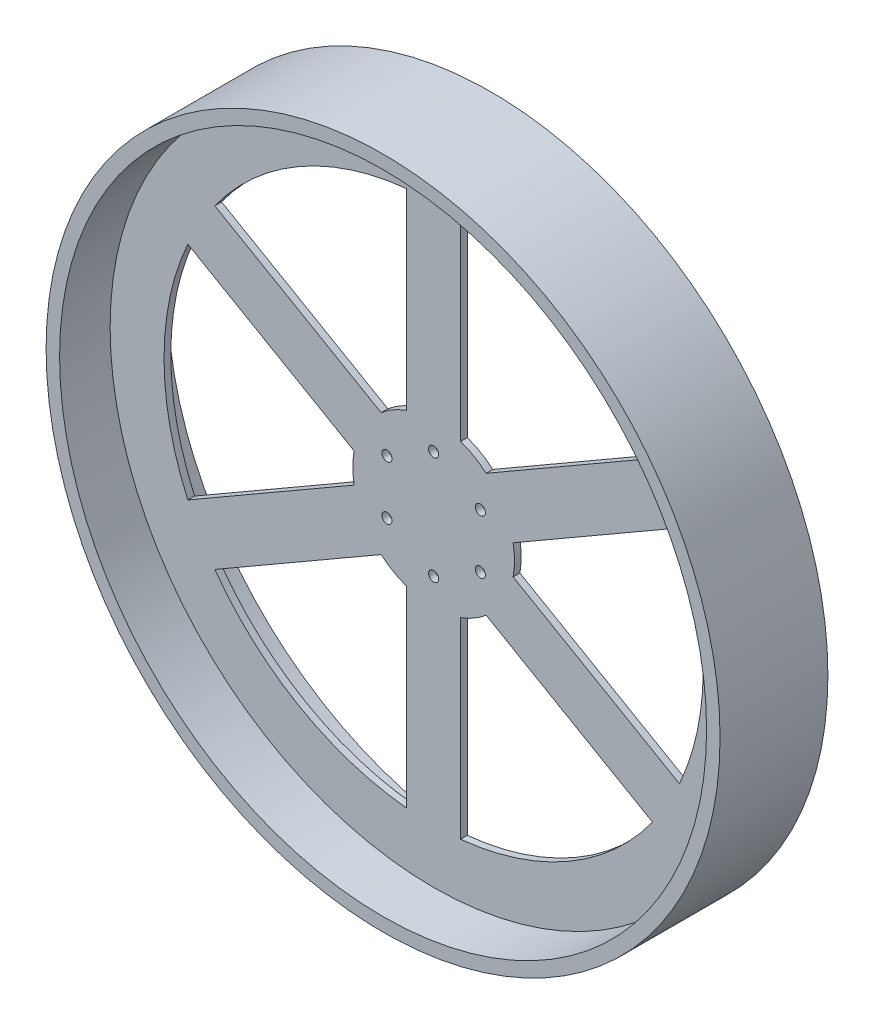
SolidWorks part; units mm, degrees
ref_plane "Front Plane" through (0, 0, 0) normal (0, 0, 1) x (1, 0, 0)
ref_plane "Top Plane" through (0, 0, 0) normal (0, 1, 0) x (1, 0, 0)
ref_plane "Right Plane" through (0, 0, 0) normal (1, 0, 0) x (0, 0, -1)
sketch "Sketch2" plane through (0, 0, 0) normal (0, 0, 1) x (1, 0, 0)
  line L0 (0, 0) -> (0, -254)
  line L1 (0, 0) -> (219.9705, -127)
  line L2 (97.2852, -85.497) -> (122.6852, -41.503) construction
  line L7 (-25.4, -127) -> (25.4, -127) construction
  line L8 (-25.4, -71.842) -> (-25.4, -252.7268)
  line L13 (25.4, -71.842) -> (25.4, -252.7268)
  line L14 (-74.917, -13.924) -> (-231.5678, -104.3664)
  line L15 (74.917, -13.924) -> (231.5678, -104.3664)
  line L16 (49.517, -57.9181) -> (206.1678, -148.3604)
  line L17 (-49.517, -57.9181) -> (-206.1678, -148.3604)
  line L18 (-49.517, 57.9181) -> (-206.1678, 148.3604)
  line L19 (-74.917, 13.924) -> (-231.5678, 104.3664)
  line L20 (25.4, 71.842) -> (25.4, 252.7268)
  line L21 (-25.4, 71.842) -> (-25.4, 252.7268)
  line L32 (74.917, 13.924) -> (231.5678, 104.3664)
  line L33 (49.517, 57.9181) -> (206.1678, 148.3604)
  circle A0 centre (0, 0) radius 304.8
  circle A1 centre (0, 0) radius 254
  circle A3 centre (0, 0) radius 254
  circle A5 centre (0, 0) radius 254
  circle A7 centre (0, 0) radius 254
  circle A9 centre (0, 0) radius 254
  circle A11 centre (0, 0) radius 254
  circle A12 centre (0, 0) radius 76.2
  point P5 (0, -127)
  point P10 (109.9852, -63.5)
  point P12 (109.9852, -63.5)
  point P14 (0, -127)
  point P17 (-25.4, -127)
  point P21 (25.4, -127)
  point P24 (97.2852, -85.497)
  point P28 (122.6852, -41.503)
  point P50 (0, 0)
  point P73 (0, 0)
  dimension "D1" = 60
  dimension "D3" = 609.6
  dimension "D2" = 508
  dimension "D4" = 152.4
  dimension "D5" = 50.8
  dimension "D6" = 3
extrude "Boss-Extrude1" add sketch "Sketch2" along direction (0, 0, 1) on the side of the normal blind 3.175 and the other way blind 3.175 contours A0 A1 | A1 | A1 | A1 | A1 L1 | L1 A1 | L0 A1 | A1 L0 | L0 L1 | L0 L1 | A1 region at (24.2552, -42.0113, 0) region at (-4.851, 8.4023, 0) region at (12.7362, -164.1659, 0) region at (-12.7362, -164.1659, 0) region at (148.54, -71.0531, 0) region at (135.8038, -93.1128, 0) region at (-142.1719, -82.083, 0) region at (142.1719, 82.083, 0) region at (-142.1719, 82.083, 0) region at (0, 164.1659, 0) region at (-296.179, 0, 0)
sketch "Sketch5" plane through (0, 0, 0) normal (0, 0, 1) x (1, 0, 0)
  circle A0 centre (0, 0) radius 317.5
  circle A1 centre (0, 0) radius 304.8
extrude "Boss-Extrude2" add sketch "Sketch5" along normal blind 50.8 and the other way blind 50.8
sketch "Sketch6" plane through (0, 0, 3.175) normal (0, 0, 1) x (1, 0, 0)
  circle A1 centre (0, 50.8) radius 4.7625
  circle A2 centre (43.9941, 25.4) radius 4.7625
  circle A3 centre (43.9941, -25.4) radius 4.7625
  circle A4 centre (0, -50.8) radius 4.7625
  circle A5 centre (-43.9941, -25.4) radius 4.7625
  circle A6 centre (-43.9941, 25.4) radius 4.7625
  point P15 (0, 0)
  dimension "D1" = 6
extrude "Cut-Extrude1" cut sketch "Sketch6" against normal through all
